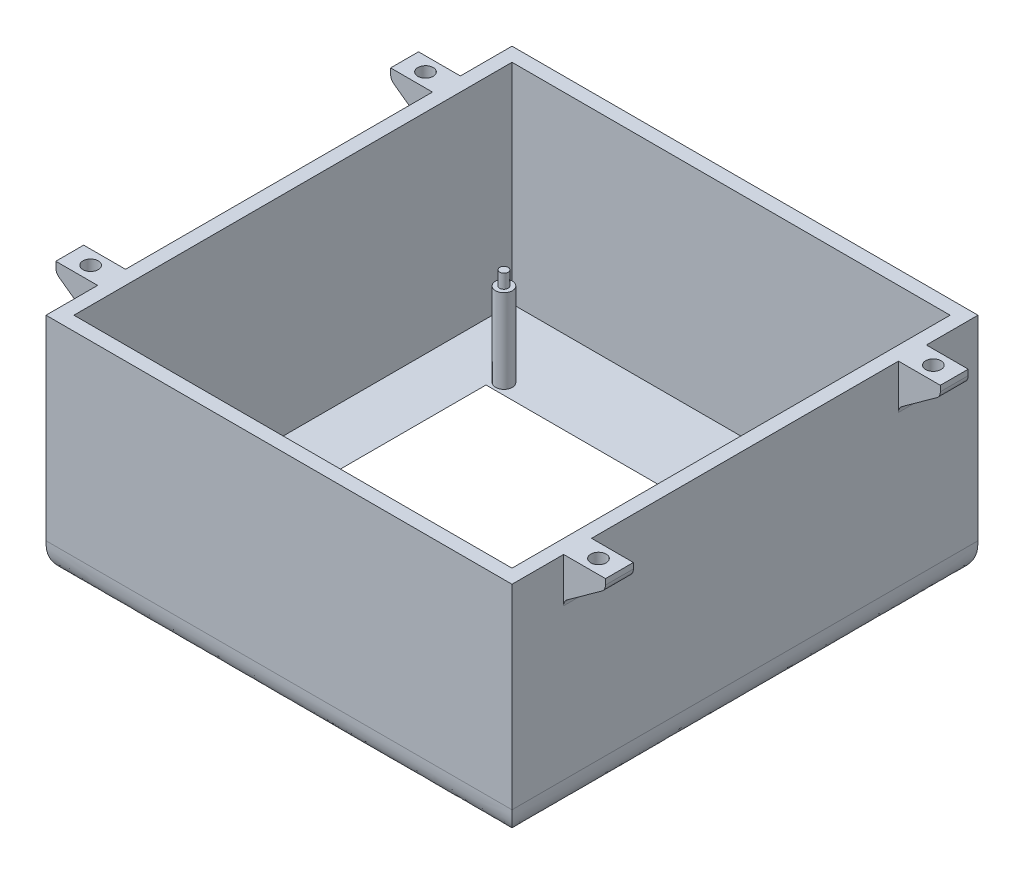
SolidWorks part; units mm, degrees
ref_plane "Ebene vorne" through (0, 0, 0) normal (0, 0, 1) x (1, 0, 0)
ref_plane "Ebene oben" through (0, 0, 0) normal (0, 1, 0) x (1, 0, 0)
ref_plane "Ebene rechts" through (0, 0, 0) normal (1, 0, 0) x (0, 0, -1)
sketch "Skizze1" plane through (0, 0, 0) normal (0, 1, 0) x (1, 0, 0)
  line L0 (-57.4441, 0) -> (108.4227, 0) construction
  line L1 (-83.5, 83.5) -> (83.5, 83.5)
  line L2 (-83.5, 83.5) -> (-83.5, -83.5)
  line L3 (-83.5, -83.5) -> (83.5, -83.5)
  line L4 (83.5, 83.5) -> (83.5, -83.5)
  line L5 (0, 55.397) -> (0, -92.4842) construction
  dimension "D1" = 167
  dimension "D2" = 167
extrude "Aufsatz-Linear austragen1" add sketch "Skizze1" along normal blind 80
sketch "Skizze2" plane through (0, 80, 0) normal (0, 1, 0) x (1, 0, 0)
  line L0 (0, 52.0751) -> (0, -71.1014) construction
  line L1 (-78.5, 78.5) -> (78.5, 78.5)
  line L2 (-78.5, 78.5) -> (-78.5, -78.5)
  line L3 (-78.5, -78.5) -> (78.5, -78.5)
  line L4 (78.5, 78.5) -> (78.5, -78.5)
  line L5 (-41.5118, 0) -> (56.2139, 0) construction
  line L6 (-83.5, 83.5) -> (-83.5, -83.5) construction
  line L7 (83.5, 83.5) -> (-83.5, 83.5) construction
  dimension "D1" = 5
  dimension "D2" = 5
extrude "Schnitt-Linear austragen1" cut sketch "Skizze2" against normal blind 75
sketch "Platine" plane through (0, 5, 0) normal (0, 1, 0) x (1, 0, 0)
  line L0 (0, 25.5089) -> (0, -13.445) construction
  line L1 (-17.8492, 0) -> (15.1436, 0) construction
  line L2 (33.515, 54.5281) -> (33.515, -95.4394) construction
  line L3 (58.415, 73.5618) -> (58.415, -76.4057) construction
  line L6 (24.1073, 11.505) -> (87.4465, 11.505) construction
  line L7 (33.8429, -13.445) -> (97.1821, -13.445) construction
  line L8 (-58.415, 56.095) -> (33.515, 56.095)
  line L9 (33.515, 56.095) -> (58.415, 11.505)
  line L10 (58.415, 11.505) -> (58.415, -13.445)
  line L11 (58.415, -13.445) -> (33.515, -56.095)
  line L12 (33.515, -56.095) -> (-58.415, -56.095)
  line L13 (-58.415, -56.095) -> (-58.415, 56.095)
  point P8 (0, 0)
  point P19 (59.508, 11.505)
  dimension "D1" = 112.19
  dimension "D2" = 91.93
  dimension "D3" = 24.9
  dimension "D4" = 44.59
  dimension "D5" = 24.95
sketch "Skizze4" plane through (0, 5, 0) normal (0, 1, 0) x (1, 0, 0)
  line L1 (-58.415, -56.095) -> (-58.415, 56.095) construction
  line L2 (-58.415, 56.095) -> (33.515, 56.095) construction
  line L3 (33.515, -56.095) -> (-58.415, -56.095) construction
  line L4 (58.415, 11.505) -> (58.415, -13.445) construction
  circle A0 centre (-55.535, 52.655) radius 3
  circle A1 centre (-55.535, -53.345) radius 3
  circle A2 centre (41.165, -32.845) radius 3
  circle A3 centre (41.165, 36.655) radius 3
  dimension "D9" = 6
  dimension "D10" = 6
  dimension "D11" = 6
  dimension "D12" = 6
  dimension "D1" = 2.88
  dimension "D2" = 3.44
  dimension "D3" = 2.88
  dimension "D4" = 2.75
  dimension "D5" = 19.44
  dimension "D6" = 17.25
  dimension "D7" = 23.25
  dimension "D8" = 17.25
extrude "Aufsatz-Linear austragen2" add sketch "Skizze4" along normal blind 30
sketch "Skizze5" plane through (0, 35, 0) normal (0, 1, 0) x (1, 0, 0)
  circle A0 centre (-55.535, 52.655) radius 1.5
  circle A1 centre (41.165, 36.655) radius 1.5
  circle A2 centre (41.165, -32.845) radius 1.5
  circle A3 centre (-55.535, -53.345) radius 1.5
  dimension "D1" = 3
  dimension "D2" = 3
  dimension "D3" = 3
  dimension "D4" = 3
extrude "Aufsatz-Linear austragen3" add sketch "Skizze5" along normal blind 5
sketch "Skizze6" plane through (0, 0, 0) normal (0, -1, 0) x (1, 0, 0)
  line L1 (-56.991, 47.6783) -> (36.8119, 47.6783)
  line L2 (-56.991, 47.6783) -> (-56.991, -47.6783)
  line L3 (-56.991, -47.6783) -> (36.8119, -47.6783)
  line L4 (36.8119, 47.6783) -> (36.8119, -47.6783)
  line L5 (0, 0) -> (0, 41.5649) construction
  line L6 (0, 0) -> (-36.8563, 0) construction
extrude "Schnitt-Linear austragen2" cut sketch "Skizze6" against normal blind 5
chamfer "Fase2" distance 6 angle 45 4 edges at (-10.0896, 0, 47.6783) (-56.991, 0, 0) (36.8119, 0, 0) (-10.0896, 0, -47.6783)
sketch "Skizze10" plane through (0, 80, 0) normal (0, 1, 0) x (1, 0, 0)
  line L0 (0, 0) -> (-140.2518, 0) construction
  line L1 (-140.2518, 0) -> (174.1265, 0) construction
  line L2 (0, 0) -> (0, -99.0125) construction
  line L3 (0, -99.0125) -> (0, 90.3805) construction
  line L4 (-83.5, 83.5) -> (-83.5, -83.5) construction
  line L5 (-83.5, 65) -> (-98.5, 65)
  line L6 (-83.5, 65) -> (-83.5, 55)
  line L7 (-83.5, 55) -> (-98.5, 55)
  line L8 (-98.5, 65) -> (-98.5, 55)
  line L9 (-83.5, -55) -> (-98.5, -55)
  line L10 (-98.5, -65) -> (-98.5, -55)
  line L11 (-83.5, -65) -> (-98.5, -65)
  line L12 (-83.5, -65) -> (-83.5, -55)
  line L13 (83.5, -65) -> (83.5, -55)
  line L14 (83.5, -65) -> (98.5, -65)
  line L15 (98.5, -65) -> (98.5, -55)
  line L16 (83.5, -55) -> (98.5, -55)
  line L17 (98.5, 65) -> (98.5, 55)
  line L18 (83.5, 55) -> (98.5, 55)
  line L19 (83.5, 65) -> (83.5, 55)
  line L20 (83.5, 65) -> (98.5, 65)
  line L21 (91, 65) -> (91, 55) construction
  line L22 (98.5, 60) -> (83.5, 60) construction
  circle A0 centre (91, 60) radius 2.75
  circle A1 centre (91, -60) radius 2.75
  circle A2 centre (-91, -60) radius 2.75
  circle A3 centre (-91, 60) radius 2.75
  point P30 (91, 59.0323)
  dimension "D3" = 5.5
  dimension "D1" = 15
  dimension "D2" = 10
  dimension "D4" = 60
extrude "Aufsatz-Linear austragen4" add sketch "Skizze10" against normal blind 20
sketch "Skizze11" plane through (0, 0, -83.5) normal (0, 0, -1) x (-1, 0, 0)
  line L3 (0, 0) -> (0, 80) construction
  line L4 (-83.5, 80) -> (83.5, 80) construction
  line L7 (83.5, 65.6081) -> (98.5, 76.4455)
  line L8 (98.5, 60) -> (98.5, 80) construction
  line L9 (83.5, 80) -> (83.5, 0) construction
  line L10 (83.5, 65.6081) -> (83.5, 60)
  line L11 (83.5, 60) -> (98.5, 60)
  line L12 (98.5, 60) -> (98.5, 76.4455)
  line L13 (-98.5, 60) -> (-98.5, 76.4455)
  line L14 (-83.5, 60) -> (-98.5, 60)
  line L15 (-83.5, 65.6081) -> (-83.5, 60)
  line L16 (-83.5, 65.6081) -> (-98.5, 76.4455)
extrude "Schnitt-Linear austragen9" cut sketch "Skizze11" against normal through all
ref_plane "Ebene1" through (0, 74, 0) normal (0, 1, 0) x (1, 0, 0)
sketch "Skizze13" plane through (0, 74, 0) normal (0, 1, 0) x (1, 0, 0)
  line L0 (0, 0) -> (0, 94.861) construction
  line L1 (0, 94.861) -> (0, -99.5436) construction
  line L2 (96.6502, 0) -> (-112.8768, 0) construction
  circle A0 centre (91, 60) radius 4.5
  circle A1 centre (91, -60) radius 4.5
  circle A2 centre (-91, -60) radius 4.5
  circle A3 centre (-91, 60) radius 4.5
  dimension "D1" = 9
extrude "Schnitt-Linear austragen10" cut sketch "Skizze13" against normal blind 8
fillet "Verrundung3" radius 3 8 edges at (83.5, 65.6081, 60) (83.5, 65.6081, -60) (-83.5, 65.6081, 60) (-83.5, 65.6081, -60) (-98.5, 76.4455, -60) (-98.5, 76.4455, 60) (98.5, 76.4455, -60) (98.5, 76.4455, 60)
fillet "Verrundung4" radius 10 4 edges at (-83.5, 0, 0) (0, 0, -83.5) (0, 0, 83.5) (83.5, 0, 0) curvature continuous yes
